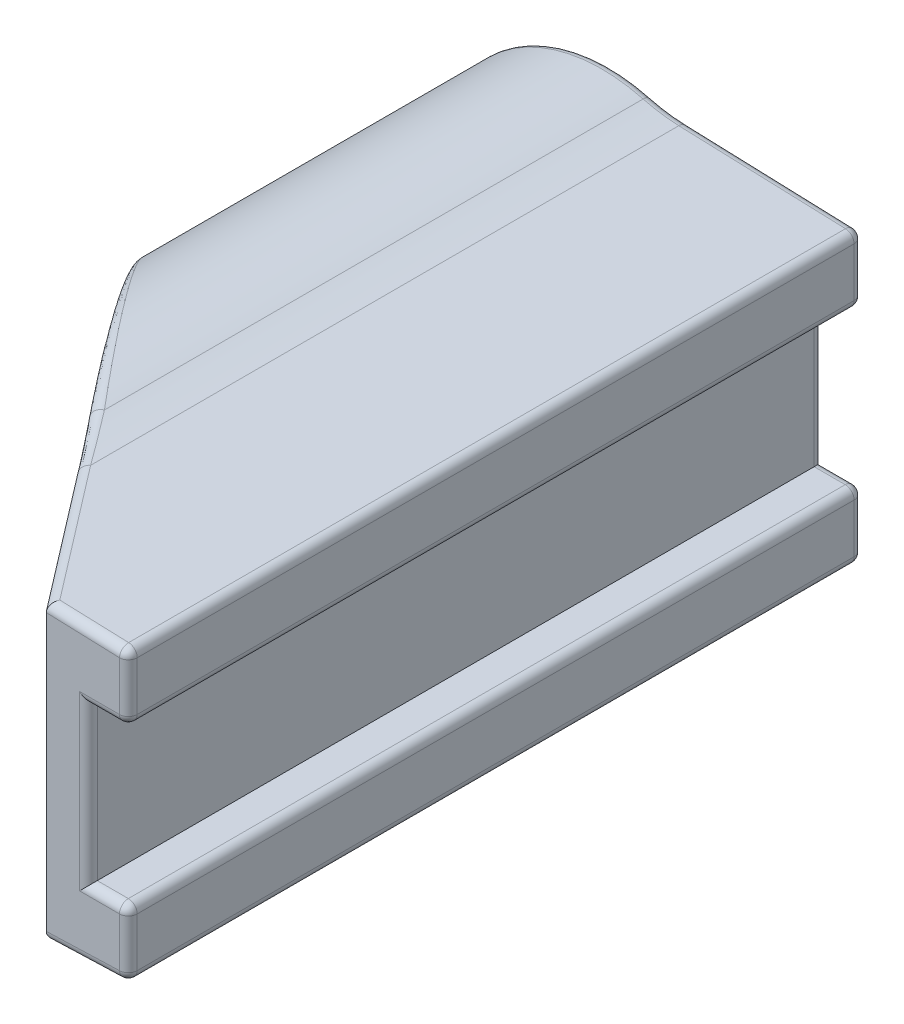
SolidWorks part; units mm, degrees
material "2024-T4"
ref_plane "Front Plane" through (0, 0, 0) normal (0, 0, 1) x (1, 0, 0)
ref_plane "Top Plane" through (0, 0, 0) normal (0, 1, 0) x (1, 0, 0)
ref_plane "Right Plane" through (0, 0, 0) normal (1, 0, 0) x (0, 0, -1)
sketch "Sketch1" plane through (0, 0, 0) normal (0, 0, 1) x (1, 0, 0)
  line L0 (34.6971, 67.6838) -> (113.7, 64.925)
  line L1 (113.7, 64.925) -> (113.7, -64.925)
  line L2 (113.7, -64.925) -> (34.6971, -67.6838)
  arc A0 (18.6136, 70.0698) -> (18.6136, -70.0698) centre (0, 0) ccw
  arc A1 (34.6971, -67.6838) -> (18.6136, -70.0698) centre (37.2273, -140.1397) ccw
  arc A2 (18.6136, 70.0698) -> (34.6971, 67.6838) centre (37.2273, 140.1397) ccw
  point P5 (113.7, 0)
  dimension "D1" = 145
  dimension "D4" = 72.5
  dimension "D2" = 129.85
  dimension "D3" = 113.7
  dimension "D5" = 92
  dimension "D6" = 92
extrude "Boss-Extrude2" add sketch "Sketch1" along normal blind 331.1 contours L0 L1 L2 A1 A0 A2
sketch "Sketch2" plane through (0, 0, 0) normal (0, 1, 0) x (1, 0, 0)
  line L0 (76.7, -331.1) -> (-72.5, -135)
  line L1 (113.7, -331.1) -> (113.7, 0) construction
  line L2 (113.7, -331.1) -> (113.7, 0) construction
  line L3 (113.7, -331.1) -> (76.7, -331.1)
  line L4 (113.7, 0) -> (-72.5, 0) construction
  line L5 (-72.5, 0) -> (-72.5, -135) construction
  line L6 (-72.5, 0) -> (-72.5, -331.1) construction
  line L7 (-72.5, -135) -> (-237.6416, -215.3365)
  line L8 (-237.6416, -215.3365) -> (-172.936, -393.1763)
  line L9 (-172.936, -393.1763) -> (76.7, -331.1)
  dimension "D1" = 135
  dimension "D2" = 37
extrude "Cut-Extrude1" cut sketch "Sketch2" against normal mid plane 200 contours L0 L7 L8 L9
sketch "Sketch3" plane through (0, 0, 0) normal (0, 0, -1) x (-1, 0, 0)
  circle A0 centre (0, 0) radius 61.5
  dimension "D1" = 123
extrude "Cut-Extrude2" cut sketch "Sketch3" against normal blind 400
sketch "Sketch4" plane through (113.7, 0, 0) normal (1, 0, 0) x (0, 0, -1)
  line L0 (0, 64.925) -> (0, -64.925) construction
  line L1 (0, -34.925) -> (-331.1, -34.925)
  line L2 (0, -34.925) -> (0, 34.925)
  line L3 (0, 34.925) -> (-331.1, 34.925)
  line L4 (-331.1, -34.925) -> (-331.1, 34.925)
  line L5 (-331.1, 64.925) -> (-331.1, -64.925) construction
  line L7 (-331.1, -64.925) -> (0, -64.925) construction
  dimension "D1" = 69.85
  dimension "D2" = 30
extrude "Cut-Extrude3" cut sketch "Sketch4" against normal blind 18
fillet "Fillet1" radius 4 28 edges at (55.6985, -66.9505, 303.4969) (26.5883, -68.4245, 265.236) (-72.5, 0, 135) (26.5883, 68.4245, 265.236) (74.1985, 66.3044, 0) (26.5883, 68.4245, 0) (-72.5, 0, 0) (26.5883, -68.4245, 0) (-61.5, 0, 149.4578) (55.6985, 66.9505, 303.4969) (95.2, 65.571, 331.1) (95.2, -65.571, 331.1) (113.7, 49.925, 331.1) (113.7, -49.925, 331.1) (113.7, 64.925, 165.55) (113.7, -49.925, 0) (113.7, 49.925, 0) (74.1985, -66.3044, 0) (113.7, -64.925, 165.55) (-61.5, 0, 0) (104.7, 34.925, 331.1) (95.7, 0, 331.1) (104.7, -34.925, 331.1) (113.7, 34.925, 165.55) (113.7, -34.925, 165.55) (104.7, -34.925, 0) (104.7, 34.925, 0) (95.7, 0, 0)
